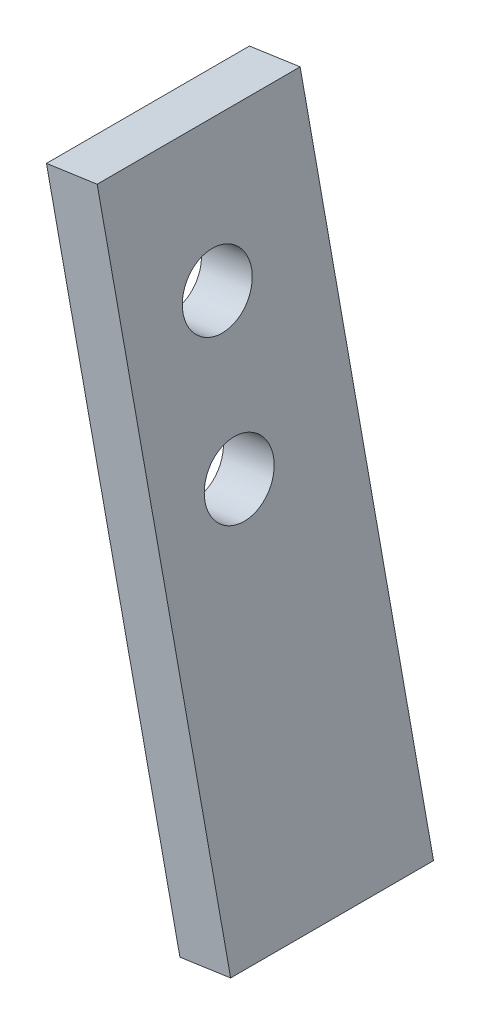
SolidWorks part; units mm, degrees
ref_plane "Front" through (0, 0, 0) normal (0, 0, 1) x (1, 0, 0)
ref_plane "Top" through (0, 0, 0) normal (0, 1, 0) x (1, 0, 0)
ref_plane "Right" through (0, 0, 0) normal (1, 0, 0) x (0, 0, -1)
ref_axis "Axis1" through (38.6204, -344.4414, 4.2776) along (-1, 0, 0)
ref_axis "Axis2" through (40.331, -22.98, 75.0619) along (-0.9898, -0.1426, 0)
ref_axis "Axis3" through (38.1486, -8.1395, 75.0619) along (-0.9898, -0.1426, 0)
ref_point "Point1"
ref_plane "Plane3" through (-15.2153, -2.5724, 84.9119) normal (-0.9898, -0.1426, 0) x (0, 0, 1)
sketch "Sketch2" plane through (-15.2153, -2.5724, 84.9119) normal (-0.9898, -0.1426, 0) x (0, 0, 1)
  line L0 (0, 0) -> (-19.8107, 0.0127)
  line L1 (-19.8107, 0.0127) -> (-23.557, -64.9849)
  line L2 (-23.557, -64.9849) -> (-3.7522, -64.9976)
  line L3 (-19.8107, 0.0127) -> (0, 0) construction
  line L4 (-19.8107, 0.0127) -> (-24.3108, -78.0635) construction
  line L5 (-4.5039, -78.0202) -> (0, 0) construction
  line L6 (-9.85, -13.1219) -> (-9.85, -28.1219) construction
  line L7 (-3.7522, -64.9976) -> (0, 0)
  circle A2 centre (-9.85, -13.1219) radius 3.3779 construction
  circle A3 centre (-9.85, -28.1219) radius 3.3779 construction
  circle A4 centre (-9.85, -13.1219) radius 3.3779
  circle A5 centre (-9.85, -28.1219) radius 3.3779
  point P11 (-9.85, -28.1219)
  point P13 (-9.85, -13.1219)
  dimension "D2" = 6.7558
  dimension "D3" = 6.7558
  dimension "D1" = 65
extrude "Boss-Extrude1" add sketch "Sketch2" against normal blind 5
equation "\"D3@Sketch2\"=\"D2@Sketch2\""
